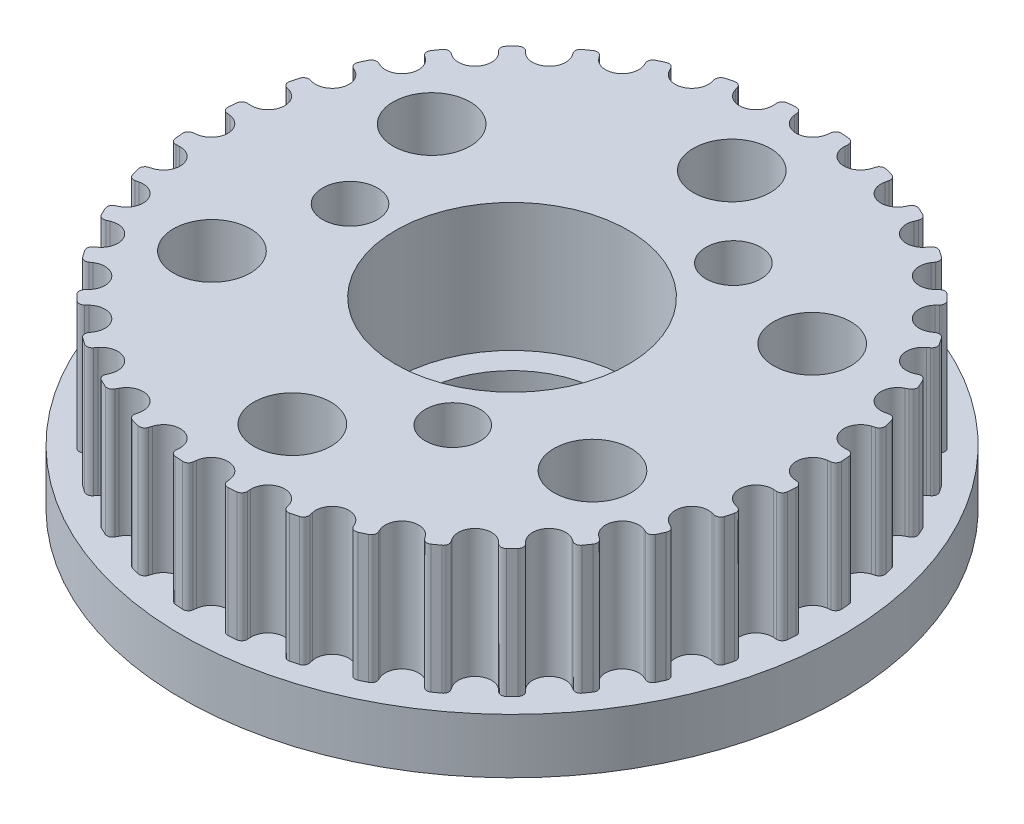
SolidWorks part; units mm, degrees
material "petg"
ref_plane "前视基准面" through (0, 0, 0) normal (0, 0, 1) x (1, 0, 0)
ref_plane "上视基准面" through (0, 0, 0) normal (0, 1, 0) x (1, 0, 0)
ref_plane "右视基准面" through (0, 0, 0) normal (1, 0, 0) x (0, 0, -1)
ref_axis "基准轴1" through (0, -44, 0) along (0, 1, 0)
sketch "草图1" plane through (0, 0, 0) normal (0, 1, 0) x (1, 0, 0)
  circle A0 centre (0, 0) radius 16.8
extrude "凸台-拉伸1" add sketch "草图1" along normal mid plane 7
sketch "草图2" plane through (0, 0, 0) normal (0, 1, 0) x (1, 0, 0)
  line B0 (-0.9032, 16.3191) -> (-0.9244, 16.4912)
  line B1 (0.9032, 16.3191) -> (0.9244, 16.4912)
  arc B2 (-0.9032, 16.3191) -> (0.9032, 16.3191) centre (0, 16.43) ccw
  arc B3 (-1.2443, 16.7539) -> (1.2443, 16.7539) centre (0, 0) cw
  arc B4 (-0.9244, 16.4912) -> (-1.2443, 16.7539) centre (-1.2221, 16.4547) ccw
  arc B5 (1.2443, 16.7539) -> (0.9244, 16.4912) centre (1.2221, 16.4547) ccw
sketch_block_instance "HTD-1"
sketch_block "HTD" parameters "OD"=33.6, "D4"=0.3, "Rb"=0.91, "Rt"=0.3, "Dh"=1.28, "deg"=14
extrude "切除-拉伸1" cut sketch "草图2" against normal mid plane 100
pattern_circular "阵列(圆周)1" count 36 over 360 about axis through (0, -44, 0) along (0, 1, 0) of "切除-拉伸1"
sketch "草图4" plane through (0, 0, 0) normal (0, 1, 0) x (1, 0, 0)
  circle A0 centre (0, 0) radius 6.35
extrude "切除-拉伸2" cut sketch "草图4" against normal mid plane 100
sketch "草图5" plane through (0, 3.5, 0) normal (0, 1, 0) x (1, 0, 0)
  line L0 (0, 0) -> (50000, 0) construction
  line L1 (0, 0) -> (0, 50000) construction
  line L2 (0, 0) -> (4.6558, 8.0641) construction
  circle A1 centre (0, 0) radius 12 construction
  circle A2 centre (0, 0) radius 8.85 construction
  circle A3 centre (0, 12) radius 2.1
  circle A4 centre (10.3923, 6) radius 2.1
  circle A5 centre (10.3923, -6) radius 2.1
  circle A6 centre (0, -12) radius 2.1
  circle A7 centre (-10.3923, -6) radius 2.1
  circle A8 centre (-10.3923, 6) radius 2.1
  circle A9 centre (4.425, 7.6643) radius 1.5
  circle A10 centre (4.425, -7.6643) radius 1.5
  circle A11 centre (-8.85, 0) radius 1.5
  point P19 (0, 0)
  point P31 (0, 0)
  dimension "D1" = 4.2
  dimension "D2" = 24
  dimension "D3" = 17.7
  dimension "D4" = 6
  dimension "D6" = 3
  dimension "D5" = 60
extrude "切除-拉伸4" cut sketch "草图5" against normal through all
ref_plane "基准面1" through (0, -3.5, 0) normal (0, 1, 0) x (1, 0, 0)
sketch "草图6" plane through (0, -3.5, 0) normal (0, -1, 0) x (-1, 0, 0)
  circle A0 centre (0, 0) radius 18
  circle A1 centre (10.3923, -6) radius 2.1 construction
  circle A3 centre (10.3923, 6) radius 2.1 construction
  circle A4 centre (10.3923, -6) radius 2.1
  circle A6 centre (10.3923, 6) radius 2.1
  circle A7 centre (0, -12) radius 2.1 construction
  circle A9 centre (-10.3923, -6) radius 2.1 construction
  circle A10 centre (-10.3923, 6) radius 2.1 construction
  circle A12 centre (0, 12) radius 2.1 construction
  circle A13 centre (0, -12) radius 2.1
  circle A15 centre (-10.3923, -6) radius 2.1
  circle A16 centre (-10.3923, 6) radius 2.1
  circle A18 centre (0, 12) radius 2.1
  dimension "D1" = 36
extrude "凸台-拉伸2" add sketch "草图6" along normal blind 3 separate body
sketch "草图7" plane through (0, -6.5, 0) normal (0, -1, 0) x (1, 0, 0)
  line L2 (0, 0) -> (29.4538, 0) construction
  line L5 (3.8098, 8.871) -> (4.9817, 9.4667)
  line L6 (5.7076, 9.0477) -> (5.7776, 7.7349)
  line L7 (3.7057, 8.8004) -> (2.5949, 7.8209)
  line L8 (3.1752, 11.8501) -> (3.7506, 13.9976)
  line L9 (5.7685, 7.6094) -> (5.4756, 6.1577)
  line L10 (8.5899, 8.5899) -> (10.247, 10.247)
  line L11 (3.9002, 11.2831) -> (6.4236, 12.6787)
  line L12 (9.5875, 1.1361) -> (10.6893, 0.4191)
  line L13 (7.7418, 9.0172) -> (8.1451, 11.7189)
  line L14 (10.6893, -0.4191) -> (9.5875, -1.1361)
  line L15 (9.4742, 1.1909) -> (8.0705, 1.6632)
  line L16 (11.8501, 3.1752) -> (13.9976, 3.7506)
  line L17 (9.4742, -1.1909) -> (8.0705, -1.6632)
  line L18 (11.734, -3.1441) -> (13.9976, -3.7506)
  line L19 (11.7216, 2.2639) -> (14.1919, 0.7763)
  line L20 (11.6801, -2.196) -> (14.2214, -1.1944)
  line L21 (5.7776, -7.7349) -> (5.7076, -9.0477)
  line L22 (4.9817, -9.4667) -> (3.8098, -8.871)
  line L23 (5.7685, -7.6094) -> (5.4756, -6.1577)
  line L24 (8.6749, -8.6749) -> (10.247, -10.247)
  line L25 (3.7057, -8.8004) -> (2.5949, -7.8209)
  line L26 (3.1441, -11.734) -> (3.7506, -13.9976)
  line L27 (7.8214, -9.0192) -> (7.7683, -11.9024)
  line L28 (3.9383, -11.2132) -> (6.0763, -12.9133)
  line L29 (-3.8098, -8.871) -> (-4.9817, -9.4667)
  line L30 (-5.7076, -9.0477) -> (-5.7776, -7.7349)
  line L31 (-3.7057, -8.8004) -> (-2.5949, -7.8209)
  line L32 (-3.1752, -11.8501) -> (-3.7506, -13.9976)
  line L33 (-5.7685, -7.6094) -> (-5.4756, -6.1577)
  line L34 (-8.5899, -8.5899) -> (-10.247, -10.247)
  line L35 (-3.9002, -11.2831) -> (-6.4236, -12.6787)
  line L36 (-7.7418, -9.0172) -> (-8.1451, -11.7189)
  line L37 (-9.5875, -1.1361) -> (-10.6893, -0.4191)
  line L38 (-10.6893, 0.4191) -> (-9.5875, 1.1361)
  line L39 (-9.4742, -1.1909) -> (-8.0705, -1.6632)
  line L40 (-11.8501, -3.1752) -> (-13.9976, -3.7506)
  line L41 (-9.4742, 1.1909) -> (-8.0705, 1.6632)
  line L42 (-11.734, 3.1441) -> (-13.9976, 3.7506)
  line L43 (-11.7216, -2.2639) -> (-14.1919, -0.7763)
  line L44 (-11.6801, 2.196) -> (-14.2214, 1.1944)
  line L45 (-5.7776, 7.7349) -> (-5.7076, 9.0477)
  line L46 (-4.9817, 9.4667) -> (-3.8098, 8.871)
  line L47 (-5.7685, 7.6094) -> (-5.4756, 6.1577)
  line L48 (-8.6749, 8.6749) -> (-10.247, 10.247)
  line L49 (-3.7057, 8.8004) -> (-2.5949, 7.8209)
  line L50 (-3.1441, 11.734) -> (-3.7506, 13.9976)
  line L51 (-7.8214, 9.0192) -> (-7.7683, 11.9024)
  line L52 (-3.9383, 11.2132) -> (-6.0763, 12.9133)
  circle A0 centre (0, 0) radius 5
  arc A1 (10.2345, 10.966) -> (8.9375, 12.0466) centre (0, 0) ccw
  arc A2 (4.6739, 5.8655) -> (2.7427, 6.9805) centre (0, 0) ccw
  arc A3 (6.3948, 13.5686) -> (4.3796, 14.3464) centre (0, 0) ccw
  arc A4 (5.4756, 6.1577) -> (4.6739, 5.8655) centre (4.9855, 6.2566) cw
  arc A5 (2.5949, 7.8209) -> (2.7427, 6.9805) centre (2.9256, 7.4459) ccw
  arc A6 (5.7776, 7.7349) -> (5.7685, 7.6094) centre (5.2783, 7.7083) cw
  arc A7 (4.9817, 9.4667) -> (5.7076, 9.0477) centre (5.2083, 9.021) cw
  arc A8 (7.7418, 9.0172) -> (8.5899, 8.5899) centre (8.2363, 8.9434) ccw
  arc A9 (3.8098, 8.871) -> (3.7057, 8.8004) centre (4.0364, 8.4253) ccw
  arc A10 (8.1451, 11.7189) -> (8.9375, 12.0466) centre (8.6396, 11.6451) cw
  arc A11 (3.9002, 11.2831) -> (3.1752, 11.8501) centre (3.6582, 11.7207) cw
  arc A12 (10.247, 10.247) -> (10.2345, 10.966) centre (9.8934, 10.6005) ccw
  arc A13 (3.7506, 13.9976) -> (4.3796, 14.3464) centre (4.2336, 13.8682) cw
  arc A14 (6.4236, 12.6787) -> (6.3948, 13.5686) centre (6.1817, 13.1163) ccw
  arc A15 (14.6141, -3.3804) -> (14.9014, -1.7168) centre (0, 0) ccw
  arc A16 (7.4167, -1.115) -> (7.4167, 1.115) centre (0, 0) ccw
  arc A17 (14.9481, 1.2462) -> (14.6141, 3.3804) centre (0, 0) ccw
  arc A18 (8.0705, -1.6632) -> (7.4167, -1.115) centre (7.9111, -1.1893) cw
  arc A19 (8.0705, 1.6632) -> (7.4167, 1.115) centre (7.9111, 1.1893) ccw
  arc A20 (9.5875, -1.1361) -> (9.4742, -1.1909) centre (9.3147, -0.717) cw
  arc A21 (10.6893, 0.4191) -> (10.6893, -0.4191) centre (10.4166, 0) cw
  arc A22 (11.6801, -2.196) -> (11.734, -3.1441) centre (11.8634, -2.6611) ccw
  arc A23 (9.5875, 1.1361) -> (9.4742, 1.1909) centre (9.3147, 0.717) ccw
  arc A24 (14.2214, -1.1944) -> (14.9014, -1.7168) centre (14.4047, -1.6596) cw
  arc A25 (11.7216, 2.2639) -> (11.8501, 3.1752) centre (11.9795, 2.6923) cw
  arc A26 (13.9976, -3.7506) -> (14.6141, -3.3804) centre (14.127, -3.2677) ccw
  arc A27 (13.9976, 3.7506) -> (14.6141, 3.3804) centre (14.127, 3.2677) cw
  arc A28 (14.1919, 0.7763) -> (14.9481, 1.2462) centre (14.4499, 1.2047) ccw
  arc A29 (4.3796, -14.3464) -> (5.9639, -13.7634) centre (0, 0) ccw
  arc A30 (2.7427, -6.9805) -> (4.6739, -5.8655) centre (0, 0) ccw
  arc A31 (8.5533, -12.3224) -> (10.2345, -10.966) centre (0, 0) ccw
  arc A32 (2.5949, -7.8209) -> (2.7427, -6.9805) centre (2.9256, -7.4459) cw
  arc A33 (5.4756, -6.1577) -> (4.6739, -5.8655) centre (4.9855, -6.2566) ccw
  arc A34 (3.8098, -8.871) -> (3.7057, -8.8004) centre (4.0364, -8.4253) cw
  arc A35 (5.7076, -9.0477) -> (4.9817, -9.4667) centre (5.2083, -9.021) cw
  arc A36 (3.9383, -11.2132) -> (3.1441, -11.734) centre (3.6271, -11.6046) ccw
  arc A37 (5.7776, -7.7349) -> (5.7685, -7.6094) centre (5.2783, -7.7083) ccw
  arc A38 (6.0763, -12.9133) -> (5.9639, -13.7634) centre (5.7651, -13.3046) cw
  arc A39 (7.8214, -9.0192) -> (8.6749, -8.6749) centre (8.3213, -9.0284) cw
  arc A40 (3.7506, -13.9976) -> (4.3796, -14.3464) centre (4.2336, -13.8682) ccw
  arc A41 (10.247, -10.247) -> (10.2345, -10.966) centre (9.8934, -10.6005) cw
  arc A42 (7.7683, -11.9024) -> (8.5533, -12.3224) centre (8.2682, -11.9116) ccw
  arc A43 (-10.2345, -10.966) -> (-8.9375, -12.0466) centre (0, 0) ccw
  arc A44 (-4.6739, -5.8655) -> (-2.7427, -6.9805) centre (0, 0) ccw
  arc A45 (-6.3948, -13.5686) -> (-4.3796, -14.3464) centre (0, 0) ccw
  arc A46 (-5.4756, -6.1577) -> (-4.6739, -5.8655) centre (-4.9855, -6.2566) cw
  arc A47 (-2.5949, -7.8209) -> (-2.7427, -6.9805) centre (-2.9256, -7.4459) ccw
  arc A48 (-5.7776, -7.7349) -> (-5.7685, -7.6094) centre (-5.2783, -7.7083) cw
  arc A49 (-4.9817, -9.4667) -> (-5.7076, -9.0477) centre (-5.2083, -9.021) cw
  arc A50 (-7.7418, -9.0172) -> (-8.5899, -8.5899) centre (-8.2363, -8.9434) ccw
  arc A51 (-3.8098, -8.871) -> (-3.7057, -8.8004) centre (-4.0364, -8.4253) ccw
  arc A52 (-8.1451, -11.7189) -> (-8.9375, -12.0466) centre (-8.6396, -11.6451) cw
  arc A53 (-3.9002, -11.2831) -> (-3.1752, -11.8501) centre (-3.6582, -11.7207) cw
  arc A54 (-10.247, -10.247) -> (-10.2345, -10.966) centre (-9.8934, -10.6005) ccw
  arc A55 (-3.7506, -13.9976) -> (-4.3796, -14.3464) centre (-4.2336, -13.8682) cw
  arc A56 (-6.4236, -12.6787) -> (-6.3948, -13.5686) centre (-6.1817, -13.1163) ccw
  arc A57 (-14.6141, 3.3804) -> (-14.9014, 1.7168) centre (0, 0) ccw
  arc A58 (-7.4167, 1.115) -> (-7.4167, -1.115) centre (0, 0) ccw
  arc A59 (-14.9481, -1.2462) -> (-14.6141, -3.3804) centre (0, 0) ccw
  arc A60 (-8.0705, 1.6632) -> (-7.4167, 1.115) centre (-7.9111, 1.1893) cw
  arc A61 (-8.0705, -1.6632) -> (-7.4167, -1.115) centre (-7.9111, -1.1893) ccw
  arc A62 (-9.5875, 1.1361) -> (-9.4742, 1.1909) centre (-9.3147, 0.717) cw
  arc A63 (-10.6893, -0.4191) -> (-10.6893, 0.4191) centre (-10.4166, 0) cw
  arc A64 (-11.6801, 2.196) -> (-11.734, 3.1441) centre (-11.8634, 2.6611) ccw
  arc A65 (-9.5875, -1.1361) -> (-9.4742, -1.1909) centre (-9.3147, -0.717) ccw
  arc A66 (-14.2214, 1.1944) -> (-14.9014, 1.7168) centre (-14.4047, 1.6596) cw
  arc A67 (-11.7216, -2.2639) -> (-11.8501, -3.1752) centre (-11.9795, -2.6923) cw
  arc A68 (-13.9976, 3.7506) -> (-14.6141, 3.3804) centre (-14.127, 3.2677) ccw
  arc A69 (-13.9976, -3.7506) -> (-14.6141, -3.3804) centre (-14.127, -3.2677) cw
  arc A70 (-14.1919, -0.7763) -> (-14.9481, -1.2462) centre (-14.4499, -1.2047) ccw
  arc A71 (-4.3796, 14.3464) -> (-5.9639, 13.7634) centre (0, 0) ccw
  arc A72 (-2.7427, 6.9805) -> (-4.6739, 5.8655) centre (0, 0) ccw
  arc A73 (-8.5533, 12.3224) -> (-10.2345, 10.966) centre (0, 0) ccw
  arc A74 (-2.5949, 7.8209) -> (-2.7427, 6.9805) centre (-2.9256, 7.4459) cw
  arc A75 (-5.4756, 6.1577) -> (-4.6739, 5.8655) centre (-4.9855, 6.2566) ccw
  arc A76 (-3.8098, 8.871) -> (-3.7057, 8.8004) centre (-4.0364, 8.4253) cw
  arc A77 (-5.7076, 9.0477) -> (-4.9817, 9.4667) centre (-5.2083, 9.021) cw
  arc A78 (-3.9383, 11.2132) -> (-3.1441, 11.734) centre (-3.6271, 11.6046) ccw
  arc A79 (-5.7776, 7.7349) -> (-5.7685, 7.6094) centre (-5.2783, 7.7083) ccw
  arc A80 (-6.0763, 12.9133) -> (-5.9639, 13.7634) centre (-5.7651, 13.3046) cw
  arc A81 (-7.8214, 9.0192) -> (-8.6749, 8.6749) centre (-8.3213, 9.0284) cw
  arc A82 (-3.7506, 13.9976) -> (-4.3796, 14.3464) centre (-4.2336, 13.8682) ccw
  arc A83 (-10.247, 10.247) -> (-10.2345, 10.966) centre (-9.8934, 10.6005) cw
  arc A84 (-7.7683, 11.9024) -> (-8.5533, 12.3224) centre (-8.2682, 11.9116) ccw
  point P30 (7.518, 7.518)
  point P35 (8.2643, 12.518)
  point P38 (2.8708, 10.7138)
  point P45 (7.2462, 13.1337)
  point P208 (0, 0)
  dimension "D1" = 10
  dimension "D2" = 30
  dimension "D3" = 15
  dimension "D6" = 0.5
  dimension "D4" = 5
  dimension "D5" = 5
  dimension "D7" = 6
extrude "切除-拉伸5" cut sketch "草图7" against normal blind 10
